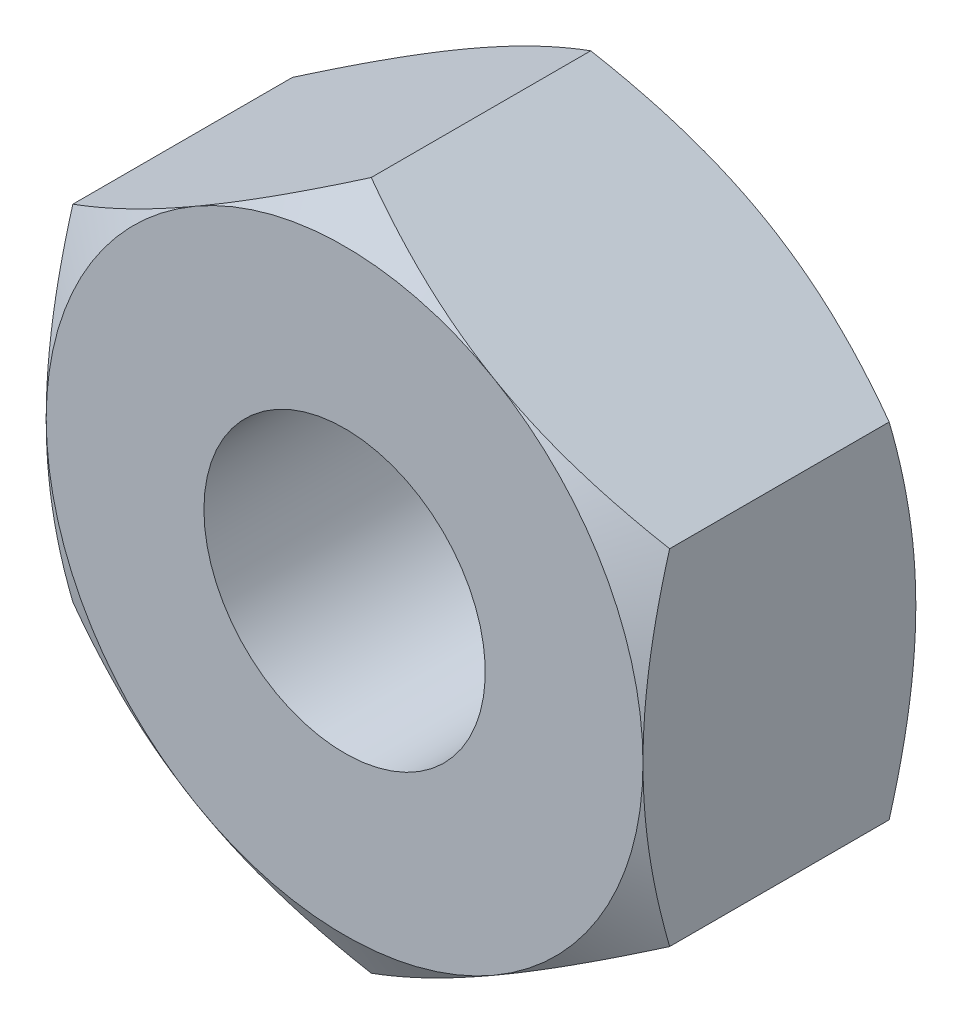
SolidWorks part; units mm, degrees
material "Acier non allié"
ref_plane "Plan1" through (0, 0, 0) normal (0, 0, 1) x (1, 0, 0)
ref_plane "Plan2" through (0, 0, 0) normal (0, 1, 0) x (1, 0, 0)
ref_plane "Plan3" through (0, 0, 0) normal (1, 0, 0) x (0, 0, -1)
sketch "Esquisse1" plane through (0, 0, 0) normal (0, 0, 1) x (1, 0, 0)
  line L0 (0, 0) -> (3.5, 0) construction
  line L1 (3.5, -2.0207) -> (3.5, 2.0207)
  line L2 (0, 0) -> (3.5, 2.0207) construction
  line L3 (0, 0) -> (0, 4.0415) construction
  line L4 (3.5, 2.0207) -> (0, 4.0415)
  line L5 (3.5, -2.0207) -> (0, -4.0415)
  line L6 (-3.5, -2.0207) -> (0, -4.0415)
  line L7 (-3.5, -2.0207) -> (-3.5, 2.0207)
  line L8 (-3.5, 2.0207) -> (0, 4.0415)
  circle A0 centre (0, 0) radius 3.5 construction
  circle A1 centre (0, 0) radius 4.0415 construction
  dimension "D2" = 7
  dimension "D1" = 30
extrude "Base-Extrusion" add sketch "Esquisse1" against normal blind 3.2
sketch "Esquisse2" plane through (0, 0, 0) normal (0, 1, 0) x (1, 0, 0)
  line L0 (-3.5, 0) -> (-7.2713, 0)
  line L1 (0, 3.2) -> (0, 0) construction
  line L2 (-3.5, 3.2) -> (-7.2713, 3.2)
  line L3 (-7.2713, 3.2) -> (-7.2713, 0)
  line L5 (-6.2713, 1.6) -> (-3.5, 3.2)
  line L6 (0, 3.2) -> (0, 0) construction
  line L7 (-3.5, 0) -> (-6.2713, 1.6)
  dimension "D1" = 30
  dimension "D2" = 1
  dimension "D3" = 30
revolve "Enlèvement de matière-Révolution1" cut sketch "Esquisse2" angle 360 about L6
hole_wizard "Trou taraudé M41" positions "Esquisse3" profile "Esquisse4" tap size "M4" standard "ISO" end condition up to next
sketch "Esquisse3" plane through (0, 0, -3.2) normal (0, 0, -1) x (-1, 0, 0)
  point P0 (0, 0)
sketch "Esquisse4" plane through (0, 0, -3.2) normal (1, 0, 0) x (0, 1, 0)
  line L0 (0, 0) -> (0, 3.2)
  line L1 (0, 3.2) -> (1.65, 3.2)
  line L2 (1.65, 3.2) -> (1.65, 0)
  line L5 (1.65, 0) -> (0, 0)
  line L11 (0, -6.35) -> (0, 107.95) construction
  dimension "Diamètre du trou pour taraudage jusqu'au prochain" = 3.3
  dimension "Profondeur du trou pour taraudage jusqu'au prochain" = 3.2
cosmetic thread "Filetage de perçage1" parameters "D2"=4
ref_axis "Axe1" through (0, 0, -50) along (0, 0, 1)
